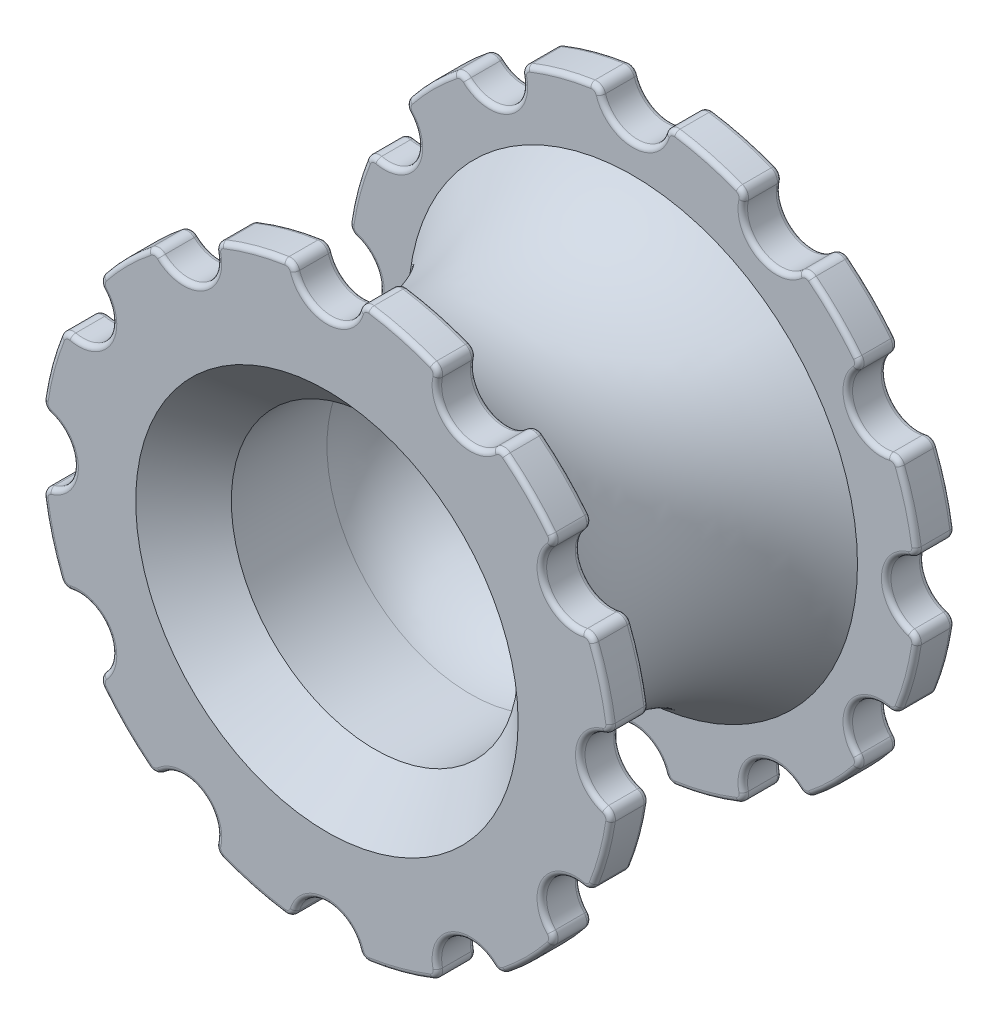
SolidWorks part; units mm, degrees
ref_plane "Спереди" through (0, 0, 0) normal (0, 0, 1) x (1, 0, 0)
ref_plane "Сверху" through (0, 0, 0) normal (0, 1, 0) x (1, 0, 0)
ref_plane "Справа" through (0, 0, 0) normal (1, 0, 0) x (0, 0, -1)
sketch "Эскиз1" plane through (0, 0, 0) normal (0, 0, 1) x (1, 0, 0)
  line L0 (0, -796.897) -> (0, 39047.9522) construction
  circle A0 centre (0, 0) radius 30 construction
  arc A1 (-3.494, 29.7958) -> (3.494, 29.7958) centre (0, 30) ccw
  arc A2 (3.494, 29.7958) -> (11.872, 27.551) centre (0, 0) cw
  arc A3 (11.872, 27.551) -> (17.9238, 24.0569) centre (15, 25.9808) ccw
  arc A4 (17.9238, 24.0569) -> (24.0569, 17.9238) centre (0, 0) cw
  arc A5 (24.0569, 17.9238) -> (27.551, 11.872) centre (25.9808, 15) ccw
  arc A6 (27.551, 11.872) -> (29.7958, 3.494) centre (0, 0) cw
  arc A7 (29.7958, 3.494) -> (29.7958, -3.494) centre (30, 0) ccw
  arc A8 (29.7958, -3.494) -> (27.551, -11.872) centre (0, 0) cw
  arc A9 (27.551, -11.872) -> (24.0569, -17.9238) centre (25.9808, -15) ccw
  arc A10 (24.0569, -17.9238) -> (17.9238, -24.0569) centre (0, 0) cw
  arc A11 (17.9238, -24.0569) -> (11.872, -27.551) centre (15, -25.9808) ccw
  arc A12 (11.872, -27.551) -> (3.494, -29.7958) centre (0, 0) cw
  arc A13 (3.494, -29.7958) -> (-3.494, -29.7958) centre (0, -30) ccw
  arc A14 (-3.494, -29.7958) -> (-11.872, -27.551) centre (0, 0) cw
  arc A15 (-11.872, -27.551) -> (-17.9238, -24.0569) centre (-15, -25.9808) ccw
  arc A16 (-17.9238, -24.0569) -> (-24.0569, -17.9238) centre (0, 0) cw
  arc A17 (-24.0569, -17.9238) -> (-27.551, -11.872) centre (-25.9808, -15) ccw
  arc A18 (-27.551, -11.872) -> (-29.7958, -3.494) centre (0, 0) cw
  arc A19 (-29.7958, -3.494) -> (-29.7958, 3.494) centre (-30, 0) ccw
  arc A20 (-29.7958, 3.494) -> (-27.551, 11.872) centre (0, 0) cw
  arc A21 (-27.551, 11.872) -> (-24.0569, 17.9238) centre (-25.9808, 15) ccw
  arc A22 (-24.0569, 17.9238) -> (-17.9238, 24.0569) centre (0, 0) cw
  arc A23 (-17.9238, 24.0569) -> (-11.872, 27.551) centre (-15, 25.9808) ccw
  arc A24 (-11.872, 27.551) -> (-3.494, 29.7958) centre (0, 0) cw
  point P55 (0, 0)
  dimension "D1" = 3.5
  dimension "D2" = 0
  dimension "D3" = 30
  dimension "D4" = 12
  dimension "D5" = 60
extrude "Бобышка-Вытянуть1" add sketch "Эскиз1" along normal blind 36
fillet "Скругление1" radius 1 24 edges at (3.494, 29.7958, 18) (11.872, 27.551, 18) (17.9238, 24.0569, 18) (29.7958, 3.494, 18) (27.551, 11.872, 18) (24.0569, 17.9238, 18) (29.7958, -3.494, 18) (27.551, -11.872, 18) (17.9238, -24.0569, 18) (24.0569, -17.9238, 18) (11.872, -27.551, 18) (-11.872, -27.551, 18) (3.494, -29.7958, 18) (-3.494, -29.7958, 18) (-17.9238, -24.0569, 18) (-24.0569, -17.9238, 18) (-27.551, -11.872, 18) (-29.7958, -3.494, 18) (-29.7958, 3.494, 18) (-27.551, 11.872, 18) (-24.0569, 17.9238, 18) (-17.9238, 24.0569, 18) (-11.872, 27.551, 18) (-3.494, 29.7958, 18)
sketch "Эскиз2" plane through (0, 0, 0) normal (0, 1, 0) x (1, 0, 0)
  line L0 (0, -1000) -> (0, 49000) construction
  line L2 (-30, -4) -> (-30, -32)
  line L5 (-30, -4) -> (-23.5, -4)
  line L6 (-30, -32) -> (-23.5, -32)
  arc A1 (-23.5, -4) -> (-23.5, -32) centre (-37.7829, -18) cw
  dimension "D3" = 6.5
  dimension "D5" = 20
  dimension "D1" = 4
  dimension "D2" = 28
  dimension "D4" = 30
revolve "Вырез-Повернуть1" cut sketch "Эскиз2" angle 360 about L0
sketch "Эскиз3" plane through (0, 0, 36) normal (0, 0, 1) x (1, 0, 0)
  circle A0 centre (0, 0) radius 15
  dimension "D1" = 30
extrude "Вырез-Вытянуть1" cut sketch "Эскиз3" against normal blind 25
fillet "Скругление2" radius 0.5 192 edges at (-29.5254, -3.7689, 4) (-26.5, 0, 4) (-29.5254, 3.7689, 4) (-28.9778, 7.7646, 4) (-27.4542, 11.4987, 4) (-22.9497, 13.25, 4) (-23.6853, 18.0266, 4) (-21.2132, 21.2132, 4) (-18.0266, 23.6853, 4) (-13.25, 22.9497, 4) (-11.4987, 27.4542, 4) (-7.7646, 28.9778, 4) (-3.7689, 29.5254, 4) (0, 26.5, 4) (3.7689, 29.5254, 4) (7.7646, 28.9778, 4) (11.4987, 27.4542, 4) (13.25, 22.9497, 4) (18.0266, 23.6853, 4) (21.2132, 21.2132, 4) (23.6853, 18.0266, 4) (22.9497, 13.25, 4) (27.4542, 11.4987, 4) (28.9778, 7.7646, 4) (29.5254, 3.7689, 4) (26.5, 0, 4) (29.5254, -3.7689, 4) (28.9778, -7.7646, 4) (27.4542, -11.4987, 4) (22.9497, -13.25, 4) (23.6853, -18.0266, 4) (21.2132, -21.2132, 4) (18.0266, -23.6853, 4) (13.25, -22.9497, 4) (11.4987, -27.4542, 4) (7.7646, -28.9778, 4) (3.7689, -29.5254, 4) (0, -26.5, 4) (-3.7689, -29.5254, 4) (-7.7646, -28.9778, 4) (-11.4987, -27.4542, 4) (-13.25, -22.9497, 4) (-18.0266, -23.6853, 4) (-21.2132, -21.2132, 4) (-23.6853, -18.0266, 4) (-22.9497, -13.25, 4) (-27.4542, -11.4987, 4) (-29.5254, -3.7689, 32) (-26.5, 0, 32) (-29.5254, 3.7689, 32) (-28.9778, 7.7646, 32) (-27.4542, 11.4987, 32) (-22.9497, 13.25, 32) (-23.6853, 18.0266, 32) (-21.2132, 21.2132, 32) (-18.0266, 23.6853, 32) (-13.25, 22.9497, 32) (-11.4987, 27.4542, 32) (-7.7646, 28.9778, 32) (-3.7689, 29.5254, 32) (0, 26.5, 32) (3.7689, 29.5254, 32) (7.7646, 28.9778, 32) (11.4987, 27.4542, 32) (13.25, 22.9497, 32) (18.0266, 23.6853, 32) (21.2132, 21.2132, 32) (23.6853, 18.0266, 32) (22.9497, 13.25, 32) (27.4542, 11.4987, 32) (28.9778, 7.7646, 32) (29.5254, 3.7689, 32) (26.5, 0, 32) (29.5254, -3.7689, 32) (28.9778, -7.7646, 32) (27.4542, -11.4987, 32) (22.9497, -13.25, 32) (23.6853, -18.0266, 32) (21.2132, -21.2132, 32) (18.0266, -23.6853, 32) (13.25, -22.9497, 32) (11.4987, -27.4542, 32) (7.7646, -28.9778, 32) (3.7689, -29.5254, 32) (0, -26.5, 32) (-3.7689, -29.5254, 32) (-7.7646, -28.9778, 32) (-11.4987, -27.4542, 32) (-13.25, -22.9497, 32) (-18.0266, -23.6853, 32) (-21.2132, -21.2132, 32) (-23.6853, -18.0266, 32) (-22.9497, -13.25, 32) (-27.4542, -11.4987, 32) (-29.5254, 3.7689, 36) (-28.9778, 7.7646, 36) (-27.4542, 11.4987, 36) (-22.9497, 13.25, 36) (-23.6853, 18.0266, 36) (-21.2132, 21.2132, 36) (-18.0266, 23.6853, 36) (-13.25, 22.9497, 36) (-11.4987, 27.4542, 36) (-7.7646, 28.9778, 36) (-3.7689, 29.5254, 36) (0, 26.5, 36) (3.7689, 29.5254, 36) (7.7646, 28.9778, 36) (11.4987, 27.4542, 36) (13.25, 22.9497, 36) (18.0266, 23.6853, 36) (21.2132, 21.2132, 36) (23.6853, 18.0266, 36) (22.9497, 13.25, 36) (27.4542, 11.4987, 36) (28.9778, 7.7646, 36) (29.5254, 3.7689, 36) (26.5, 0, 36) (29.5254, -3.7689, 36) (28.9778, -7.7646, 36) (27.4542, -11.4987, 36) (22.9497, -13.25, 36) (23.6853, -18.0266, 36) (21.2132, -21.2132, 36) (18.0266, -23.6853, 36) (13.25, -22.9497, 36) (11.4987, -27.4542, 36) (7.7646, -28.9778, 36) (3.7689, -29.5254, 36) (0, -26.5, 36) (-3.7689, -29.5254, 36) (-7.7646, -28.9778, 36) (-11.4987, -27.4542, 36) (-13.25, -22.9497, 36) (-18.0266, -23.6853, 36) (-21.2132, -21.2132, 36) (-23.6853, -18.0266, 36) (-22.9497, -13.25, 36) (-27.4542, -11.4987, 36) (-28.9778, -7.7646, 36) (-29.5254, -3.7689, 36) (3.7689, 29.5254, 0) (0, 26.5, 0) (-3.7689, 29.5254, 0) (-7.7646, 28.9778, 0) (-11.4987, 27.4542, 0) (-13.25, 22.9497, 0) (-18.0266, 23.6853, 0) (-21.2132, 21.2132, 0) (-23.6853, 18.0266, 0) (-22.9497, 13.25, 0) (-27.4542, 11.4987, 0) (-28.9778, 7.7646, 0) (-29.5254, 3.7689, 0) (-26.5, 0, 0) (-29.5254, -3.7689, 0) (-28.9778, -7.7646, 0) (-27.4542, -11.4987, 0) (-22.9497, -13.25, 0) (-23.6853, -18.0266, 0) (-21.2132, -21.2132, 0) (-18.0266, -23.6853, 0) (-13.25, -22.9497, 0) (-11.4987, -27.4542, 0) (-7.7646, -28.9778, 0) (-3.7689, -29.5254, 0) (0, -26.5, 0) (3.7689, -29.5254, 0) (7.7646, -28.9778, 0) (11.4987, -27.4542, 0) (13.25, -22.9497, 0) (18.0266, -23.6853, 0) (21.2132, -21.2132, 0) (23.6853, -18.0266, 0) (22.9497, -13.25, 0) (27.4542, -11.4987, 0) (28.9778, -7.7646, 0) (29.5254, -3.7689, 0) (26.5, 0, 0) (29.5254, 3.7689, 0) (28.9778, 7.7646, 0) (27.4542, 11.4987, 0) (22.9497, 13.25, 0) (23.6853, 18.0266, 0) (21.2132, 21.2132, 0) (18.0266, 23.6853, 0) (13.25, 22.9497, 0) (11.4987, 27.4542, 0) (7.7646, 28.9778, 0) (-28.9778, -7.7646, 4) (-28.9778, -7.7646, 32) (-26.5, 0, 36)
fillet "Скругление3" radius 10 1 edges at (15, 0, 11)
chamfer "Фаска1" distance 5 angle 45 1 edges at (15, 0, 36)
sketch "Эскиз4" plane through (0, 0, 0) normal (0, 0, -1) x (-1, 0, 0)
  circle A0 centre (0, 0) radius 6
  dimension "D1" = 12
extrude "Бобышка-Вытянуть2" add sketch "Эскиз4" along normal blind 1.5
sketch "Эскиз5" plane through (0, 0, -1.5) normal (0, 0, -1) x (-1, 0, 0)
  circle A0 centre (0, 0) radius 3.75
  dimension "D1" = 7.5
extrude "Бобышка-Вытянуть3" add sketch "Эскиз5" along normal blind 3.5
sketch "Эскиз6" plane through (0, 0, -5) normal (0, 0, -1) x (-1, 0, 0)
  circle A0 centre (0, 0) radius 2.7
  dimension "D1" = 5.4
extrude "Вырез-Вытянуть2" cut sketch "Эскиз6" against normal blind 1
sketch "Эскиз7" plane through (0, 0, -4) normal (0, 0, -1) x (-1, 0, 0)
  line L0 (-1.85, 1.9666) -> (-1.85, -1.9666)
  line L2 (1.85, 1.9666) -> (1.85, -1.9666)
  arc A0 (-1.85, -1.9666) -> (1.85, -1.9666) centre (0, 0) ccw
  circle A1 centre (0, 0) radius 2.7 construction
  arc A2 (1.85, 1.9666) -> (-1.85, 1.9666) centre (0, 0) ccw
  dimension "D1" = 3.7
extrude "Вырез-Вытянуть3" cut sketch "Эскиз7" against normal blind 8
sketch "Эскиз8" plane through (0, 0, 11) normal (0, 0, 1) x (1, 0, 0)
  circle A0 centre (0, 0) radius 1.475
  dimension "D1" = 2.95
extrude "Вырез-Вытянуть4" cut sketch "Эскиз8" against normal blind 17
